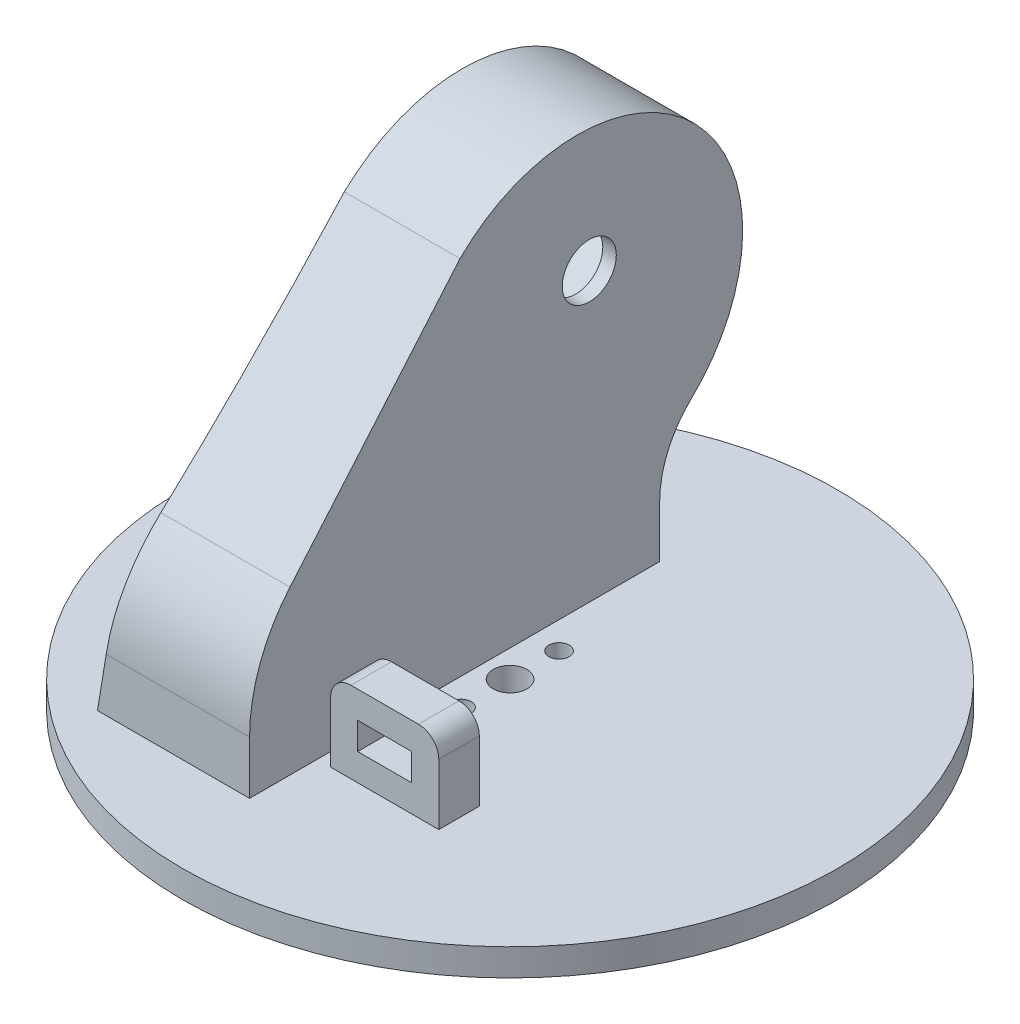
SolidWorks part; units mm, degrees
ref_plane "Front Plane" through (0, 0, 0) normal (0, 0, 1) x (1, 0, 0)
ref_plane "Top Plane" through (0, 0, 0) normal (0, 1, 0) x (1, 0, 0)
ref_plane "Right Plane" through (0, 0, 0) normal (1, 0, 0) x (0, 0, -1)
sketch "Sketch2" plane through (0, 0, 0) normal (0, 1, 0) x (1, 0, 0)
  circle A0 centre (0, 0) radius 48.5
  dimension "D1" = 97
extrude "Boss-Extrude1" add sketch "Sketch2" along normal blind 4
sketch "Sketch4" plane through (0, 0, 0) normal (0, -1, 0) x (1, 0, 0)
  circle A0 centre (0, 7.25) radius 1.5
  circle A1 centre (0, -7.25) radius 1.5
  dimension "D1" = 3
  dimension "D2" = 3
  dimension "D3" = 14.5
  dimension "D4" = 7.25
extrude "Cut-Extrude2" cut sketch "Sketch4" against normal through all
sketch "Sketch5" plane through (0, 0, 0) normal (0, -1, 0) x (1, 0, 0)
  circle A0 centre (0, 0) radius 2.5
  dimension "D1" = 5
extrude "Cut-Extrude3" cut sketch "Sketch5" against normal through all
ref_plane "Plane1" through (-4, 0, 0) normal (1, 0, 0) x (0, 0, -1)
sketch "Sketch7" plane through (-4, 0, 0) normal (1, 0, 0) x (0, 0, -1)
  line L0 (23.1299, 11.6445) -> (23.1299, 4)
  line L5 (48.5, 4) -> (-48.5, 4) construction
  line L6 (-27.2273, 29.5362) -> (-1.2843, 55.4793)
  line L7 (-43.5609, 4) -> (23.1299, 4)
  line L11 (-34.5496, 4) -> (-34.5496, 11.8586)
  arc A4 (28.7298, 24.692) -> (-1.2843, 55.4793) centre (13.9185, 40.2765) ccw
  arc A5 (28.7298, 24.692) -> (23.1299, 11.6445) centre (41.1299, 11.6445) ccw
  arc A6 (-27.2273, 29.5362) -> (-34.5496, 11.8586) centre (-9.5496, 11.8586) ccw
  dimension "D1" = 25
  dimension "D4" = 43
  dimension "D3" = 18
  dimension "D5" = 45
extrude "Boss-Extrude2" add sketch "Sketch7" against normal blind 14 contours A5 A4 L6 L7 L0 | A4 | A4 | A4 | L6 A6 L7 region at (-4, 29.3392, -2.7362)
ref_plane "Plane2" through (-6, 0, 0) normal (1, 0, 0) x (0, 0, -1)
sketch "Sketch8" plane through (-6, 0, 0) normal (1, 0, 0) x (0, 0, -1)
  line L0 (-27.2273, 29.5362) -> (-1.2843, 55.4793) construction
  line L1 (-2.5217, 38.6855) -> (13.7417, 54.9489)
  line L2 (-2.5217, 38.6855) -> (6.6707, 29.4931)
  line L3 (6.6707, 29.4931) -> (22.9341, 45.7566)
  line L4 (13.7417, 54.9489) -> (22.9341, 45.7566)
  line L5 (-2.5217, 38.6855) -> (22.9341, 45.7566) construction
  line L6 (6.6707, 29.4931) -> (13.7417, 54.9489) construction
  point P0 (10.2062, 42.221)
  point P11 (13.9185, 40.2765)
  dimension "D1" = 23
  dimension "D2" = 13
  dimension "D3" = 90
  dimension "D5" = 90
  dimension "D6" = 10.25
extrude "Cut-Extrude5" cut sketch "Sketch8" against normal up to next
sketch "Sketch9" plane through (-18, 0, 0) normal (-1, 0, 0) x (0, 0, 1)
  line L0 (-13.7417, 54.9489) -> (-22.9341, 45.7566) construction
  line L3 (-18.3379, 50.3528) -> (-19.7076, 51.7224) construction
  circle A0 centre (-17.2773, 56.3632) radius 1.3
  circle A1 centre (-24.3483, 49.2921) radius 1.3
  circle A2 centre (9.5928, 15.351) radius 1.3
  circle A3 centre (16.6639, 22.422) radius 1.3
  dimension "D1" = 2.6
  dimension "D5" = 5
  dimension "D6" = 90
  dimension "D2" = 3.5
  dimension "D3" = 2
  dimension "D4" = 2
extrude "Cut-Extrude6" cut sketch "Sketch9" against normal blind 7.5
sketch "Sketch11" plane through (-4, 0, 0) normal (1, 0, 0) x (0, 0, -1)
  circle A0 centre (15.7196, 46.4843) radius 4
  point P3 (15.7196, 46.4843)
  point P5 (13.9185, 40.2765)
extrude "Cut-Extrude9" cut sketch "Sketch11" against normal up to next
sketch "Sketch17" plane through (-18, 0, 0) normal (-1, 0, 0) x (0, 0, 1)
  line L0 (29.3486, 31.6576) -> (3.4056, 57.6006)
  line L1 (-26.1299, 11.6445) -> (-26.1299, 1)
  line L2 (-26.1299, 1) -> (37.5496, 1)
  line L3 (37.5496, 1) -> (37.5496, 11.8586)
  line L4 (27.2273, 29.5362) -> (1.2843, 55.4793)
  line L5 (-23.1299, 11.6445) -> (-23.1299, 4)
  line L6 (-23.1299, 4) -> (34.5496, 4)
  line L7 (34.5496, 4) -> (34.5496, 11.8586)
  line L9 (-23.1299, 11.6445) -> (-23.1299, 4)
  line L10 (-23.1299, 4) -> (34.5496, 4)
  line L11 (34.5496, 4) -> (34.5496, 11.8586)
  line L12 (-26.1299, 4) -> (37.5496, 4)
  line L13 (48.5, 4) -> (-48.5, 4) construction
  line L14 (3.4056, 57.6006) -> (28.5745, 28.0776)
  line L15 (1.2843, 55.4793) -> (26.295, 26.1272)
  line L16 (31.5496, 11.8586) -> (31.5496, 4)
  line L18 (27.2273, 29.5362) -> (1.2843, 55.4793) construction
  arc A0 (3.4056, 57.6006) -> (-30.7965, 22.5174) centre (-13.9185, 40.2765) ccw
  arc A1 (-26.1299, 11.6445) -> (-30.7965, 22.5174) centre (-41.1299, 11.6445) ccw
  arc A2 (37.5496, 11.8586) -> (29.3486, 31.6576) centre (9.5496, 11.8586) ccw
  arc A3 (1.2843, 55.4793) -> (-28.7298, 24.692) centre (-13.9185, 40.2765) ccw
  arc A4 (-23.1299, 11.6445) -> (-28.7298, 24.692) centre (-41.1299, 11.6445) ccw
  arc A5 (34.5496, 11.8586) -> (27.2273, 29.5362) centre (9.5496, 11.8586) ccw
  arc A6 (1.2843, 55.4793) -> (-28.7298, 24.692) centre (-13.9185, 40.2765) ccw
  arc A7 (-23.1299, 11.6445) -> (-28.7298, 24.692) centre (-41.1299, 11.6445) ccw
  arc A8 (34.5496, 11.8586) -> (27.2273, 29.5362) centre (9.5496, 11.8586) ccw
  arc A9 (31.5496, 11.8586) -> (25.106, 27.4149) centre (9.5496, 11.8586) ccw
  line M16 (27.2273, 29.5362) -> (1.2843, 55.4793)
  arc M17 (1.2843, 55.4793) -> (-28.7298, 24.692) centre (-13.9185, 40.2765) ccw
  arc M18 (-28.7298, 24.692) -> (-23.1299, 11.6445) centre (-41.1299, 11.6445) cw
  line M19 (-23.1299, 11.6445) -> (-23.1299, 4)
  line M21 (34.5496, 4) -> (34.5496, 11.8586)
  arc M22 (34.5496, 11.8586) -> (27.2273, 29.5362) centre (9.5496, 11.8586) ccw
  dimension "D1" = 0
  dimension "D2" = 3
  dimension "D3" = 3
extrude "Boss-Extrude7" add sketch "Sketch17" along normal blind 9 and the other way up to surface (14 mm away) contours A9 L16 L12 L15 M21 M22 M16 | A1 L1 L12 L14 A0 M19 M18 M17 M16 M22 region at (-18, 42.2523, 15.3017) region at (-18, 20.289, 32.4332) other way up to face at (-4, 46.4843, -19.7196)
sketch "Sketch25" plane through (-18, 0, 0) normal (-1, 0, 0) x (0, 0, 1)
  line L0 (-23.1299, 11.6445) -> (-23.1299, 4)
  line L1 (48.5, 4) -> (-48.5, 4) construction
  line L2 (-23.1299, 11.6445) -> (-23.1299, 4) construction
  line L3 (1.2843, 55.4793) -> (26.295, 26.1272) construction
  line L4 (31.5496, 4) -> (-23.1299, 4) construction
  line L5 (31.5496, 11.8586) -> (31.5496, 4) construction
  line L6 (31.5496, 4) -> (-23.1299, 4)
  line L7 (31.5496, 11.8586) -> (31.5496, 4)
  line L8 (1.2843, 55.4793) -> (26.295, 26.1272)
  arc A0 (-23.1299, 11.6445) -> (-28.7298, 24.692) centre (-41.1299, 11.6445) ccw construction
  arc A1 (1.2843, 55.4793) -> (-28.7298, 24.692) centre (-13.9185, 40.2765) ccw construction
  arc A2 (-23.1299, 11.6445) -> (-28.7298, 24.692) centre (-41.1299, 11.6445) ccw
  arc A3 (31.5496, 11.8586) -> (26.295, 26.1272) centre (9.5496, 11.8586) ccw construction
  arc A4 (31.5496, 11.8586) -> (26.295, 26.1272) centre (9.5496, 11.8586) ccw
  spline S0 degree 3 poles (-28.7298, 24.692) (-21.9549, 18.2532) (-19.0941, 12.798) (-15.1299, 4) knots 0 0 0 0 1 1 1 1
  spline S1 degree 2 poles (11.7516, 43.195) (26.5513, 25.8264) (25.5496, 4) knots 0 0 0 1 1 1
  dimension "D2" = 8
  dimension "D1" = 6
extrude "Boss-Extrude10" add sketch "Sketch25" along normal up to surface (9 mm away) contours S0 L6 L0 A2 | A4 S1 A2 S0 L8 region at (-18, 9.918, -20.706) region at (-18, 17.2593, 26.6261) up to face at (-27, 22.2911, 0.3951)
sketch "Sketch26" plane through (0, 0, 0) normal (0, 0, 1) x (1, 0, 0)
  line L0 (-4, 64.7765) -> (-27, 64.7765) construction
  line L1 (-27, 4) -> (-4, 4) construction
  line L2 (-27, 4) -> (-27, 11.8586) construction
  line L3 (-26, 64.7765) -> (-27, 64.7765)
  line L4 (-27, 64.7765) -> (-27, 4)
  line L5 (-27, 4) -> (-23, 4)
  spline S0 degree 2 poles (-26, 64.7765) (-24.7724, 34.3751) (-23, 4) knots 0 0 0 1 1 1
  dimension "D1" = 1
  dimension "D2" = 4
  dimension "D3" = 2
extrude "Cut-Extrude15" [suppressed] cut sketch "Sketch26" against normal through all both and the other way through all contours L4 L5 S0 L3
sketch "Sketch27" plane through (0, 4, 0) normal (0, 1, 0) x (1, 0, 0)
  line L1 (-2, -18.5496) -> (14, -18.5496)
  line L2 (-2, -18.5496) -> (-2, -24.5496)
  line L3 (-2, -24.5496) -> (14, -24.5496)
  line L4 (14, -18.5496) -> (14, -24.5496)
  line L5 (-27, -34.5496) -> (-4, -34.5496) construction
  line L6 (-4, -34.5496) -> (-4, 26.1299) construction
  dimension "D1" = 10
  dimension "D2" = 6
  dimension "D3" = 16
  dimension "D4" = 2
extrude "Boss-Extrude11" add sketch "Sketch27" along normal blind 12
fillet "Fillet6" radius 3 2 edges at (14, 16, 21.5496) (-2, 16, 21.5496)
sketch "Sketch28" plane through (0, 0, 24.5496) normal (0, 0, 1) x (1, 0, 0)
  line L8 (10, 12) -> (2, 12)
  line L9 (2, 12) -> (2, 8)
  line L10 (2, 8) -> (10, 8)
  line L11 (10, 8) -> (10, 12)
  line L12 (10, 12) -> (2, 12)
  line L13 (2, 12) -> (2, 8)
  line L14 (2, 8) -> (10, 8)
  line L15 (10, 8) -> (10, 12)
  dimension "D1" = 4
extrude "Cut-Extrude16" cut sketch "Sketch28" against normal up to next
sketch "Sketch29" plane through (0, 0, 0) normal (0, 0, 1) x (1, 0, 0)
  line L0 (-4, 64.7765) -> (-27, 64.7765) construction
  line L1 (-27, 4) -> (-4, 4) construction
  line L2 (-21, 64.7765) -> (-27, 64.7765)
  line L3 (-27, 64.7765) -> (-27, 4)
  line L4 (-27, 4) -> (-26.5, 4)
  line L5 (48.5, 4) -> (-48.5, 4) construction
  spline S0 degree 2 poles (-21, 64.7765) (-21.2205, 34.1409) (-26.5, 4) knots 0 0 0 1 1 1
  dimension "D1" = 6
  dimension "D2" = 4
  dimension "D3" = 0.5
  dimension "D4" = 25
extrude "Cut-Extrude17" cut sketch "Sketch29" against normal through all both and the other way through all
